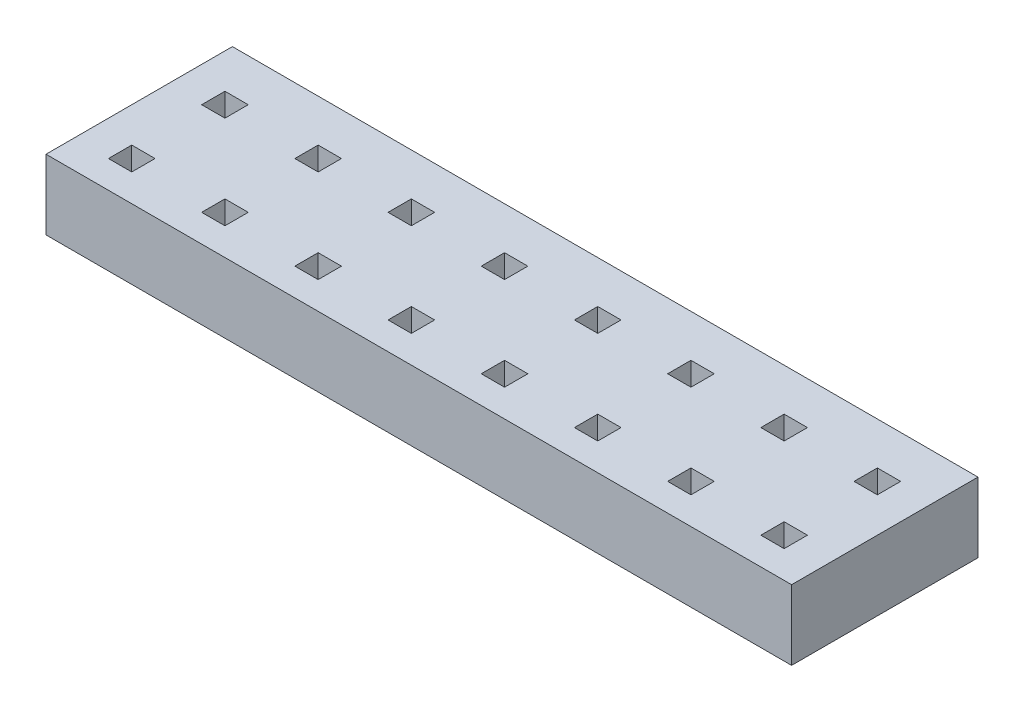
SolidWorks part; units mm, degrees
ref_plane "Front Plane" through (0, 0, 0) normal (0, 0, 1) x (1, 0, 0)
ref_plane "Top Plane" through (0, 0, 0) normal (0, 1, 0) x (1, 0, 0)
ref_plane "Right Plane" through (0, 0, 0) normal (1, 0, 0) x (0, 0, -1)
sketch "Sketch1" plane through (0, 0, 0) normal (0, 1, 0) x (1, 0, 0)
  line L1 (0, 0) -> (16, 0)
  line L2 (0, 0) -> (0, 4)
  line L3 (0, 4) -> (16, 4)
  line L4 (16, 0) -> (16, 4)
extrude "Boss-Extrude1" add sketch "Sketch1" along normal blind 1.5
sketch "Sketch2" plane through (0, 1.5, 0) normal (0, 1, 0) x (1, 0, 0)
  line L0 (2.75, 3.09) -> (3.25, 3.09)
  line L1 (0.75, 3.09) -> (1.25, 3.09)
  line L2 (0.75, 3.09) -> (0.75, 2.59)
  line L3 (0.75, 2.59) -> (1.25, 2.59)
  line L4 (1.25, 3.09) -> (1.25, 2.59)
  line L5 (2.75, 3.09) -> (2.75, 2.59)
  line L6 (2.75, 2.59) -> (3.25, 2.59)
  line L7 (3.25, 3.09) -> (3.25, 2.59)
  line L8 (4.75, 3.09) -> (5.25, 3.09)
  line L9 (4.75, 3.09) -> (4.75, 2.59)
  line L10 (4.75, 2.59) -> (5.25, 2.59)
  line L11 (5.25, 3.09) -> (5.25, 2.59)
  line L12 (6.75, 3.09) -> (7.25, 3.09)
  line L13 (6.75, 3.09) -> (6.75, 2.59)
  line L14 (6.75, 2.59) -> (7.25, 2.59)
  line L15 (7.25, 3.09) -> (7.25, 2.59)
  line L16 (8.75, 3.09) -> (9.25, 3.09)
  line L17 (8.75, 3.09) -> (8.75, 2.59)
  line L18 (8.75, 2.59) -> (9.25, 2.59)
  line L19 (9.25, 3.09) -> (9.25, 2.59)
  line L20 (10.75, 3.09) -> (11.25, 3.09)
  line L21 (10.75, 3.09) -> (10.75, 2.59)
  line L22 (10.75, 2.59) -> (11.25, 2.59)
  line L23 (11.25, 3.09) -> (11.25, 2.59)
  line L24 (12.75, 3.09) -> (13.25, 3.09)
  line L25 (12.75, 3.09) -> (12.75, 2.59)
  line L26 (12.75, 2.59) -> (13.25, 2.59)
  line L27 (13.25, 3.09) -> (13.25, 2.59)
  line L28 (14.75, 3.09) -> (15.25, 3.09)
  line L29 (14.75, 3.09) -> (14.75, 2.59)
  line L30 (14.75, 2.59) -> (15.25, 2.59)
  line L31 (15.25, 3.09) -> (15.25, 2.59)
  line L32 (16.75, 3.09) -> (17.25, 3.09)
  line L33 (16.75, 3.09) -> (16.75, 2.59)
  line L34 (16.75, 2.59) -> (17.25, 2.59)
  line L35 (17.25, 3.09) -> (17.25, 2.59)
  line L36 (18.75, 3.09) -> (19.25, 3.09)
  line L37 (18.75, 3.09) -> (18.75, 2.59)
  line L38 (18.75, 2.59) -> (19.25, 2.59)
  line L39 (19.25, 3.09) -> (19.25, 2.59)
  line L40 (20.75, 3.09) -> (21.25, 3.09)
  line L41 (20.75, 3.09) -> (20.75, 2.59)
  line L42 (20.75, 2.59) -> (21.25, 2.59)
  line L43 (21.25, 3.09) -> (21.25, 2.59)
  line L44 (22.75, 3.09) -> (23.25, 3.09)
  line L45 (22.75, 3.09) -> (22.75, 2.59)
  line L46 (22.75, 2.59) -> (23.25, 2.59)
  line L47 (23.25, 3.09) -> (23.25, 2.59)
  line L48 (24.75, 3.09) -> (25.25, 3.09)
  line L49 (24.75, 3.09) -> (24.75, 2.59)
  line L50 (24.75, 2.59) -> (25.25, 2.59)
  line L51 (25.25, 3.09) -> (25.25, 2.59)
  line L52 (26.75, 3.09) -> (27.25, 3.09)
  line L53 (26.75, 3.09) -> (26.75, 2.59)
  line L54 (26.75, 2.59) -> (27.25, 2.59)
  line L55 (27.25, 3.09) -> (27.25, 2.59)
  line L56 (28.75, 3.09) -> (29.25, 3.09)
  line L57 (28.75, 3.09) -> (28.75, 2.59)
  line L58 (28.75, 2.59) -> (29.25, 2.59)
  line L59 (29.25, 3.09) -> (29.25, 2.59)
  line L60 (30.75, 3.09) -> (31.25, 3.09)
  line L61 (30.75, 3.09) -> (30.75, 2.59)
  line L62 (30.75, 2.59) -> (31.25, 2.59)
  line L63 (31.25, 3.09) -> (31.25, 2.59)
  line L64 (32.75, 3.09) -> (33.25, 3.09)
  line L65 (32.75, 3.09) -> (32.75, 2.59)
  line L66 (32.75, 2.59) -> (33.25, 2.59)
  line L67 (33.25, 3.09) -> (33.25, 2.59)
  line L68 (34.75, 3.09) -> (35.25, 3.09)
  line L69 (34.75, 3.09) -> (34.75, 2.59)
  line L70 (34.75, 2.59) -> (35.25, 2.59)
  line L71 (35.25, 3.09) -> (35.25, 2.59)
  line L72 (0.75, 1.09) -> (1.25, 1.09)
  line L73 (0.75, 1.09) -> (0.75, 0.59)
  line L74 (0.75, 0.59) -> (1.25, 0.59)
  line L75 (1.25, 1.09) -> (1.25, 0.59)
  line L76 (2.75, 1.09) -> (3.25, 1.09)
  line L77 (2.75, 1.09) -> (2.75, 0.59)
  line L78 (2.75, 0.59) -> (3.25, 0.59)
  line L79 (3.25, 1.09) -> (3.25, 0.59)
  line L80 (4.75, 1.09) -> (5.25, 1.09)
  line L81 (4.75, 1.09) -> (4.75, 0.59)
  line L82 (4.75, 0.59) -> (5.25, 0.59)
  line L83 (5.25, 1.09) -> (5.25, 0.59)
  line L84 (6.75, 1.09) -> (7.25, 1.09)
  line L85 (6.75, 1.09) -> (6.75, 0.59)
  line L86 (6.75, 0.59) -> (7.25, 0.59)
  line L87 (7.25, 1.09) -> (7.25, 0.59)
  line L88 (8.75, 1.09) -> (9.25, 1.09)
  line L89 (8.75, 1.09) -> (8.75, 0.59)
  line L90 (8.75, 0.59) -> (9.25, 0.59)
  line L91 (9.25, 1.09) -> (9.25, 0.59)
  line L92 (10.75, 1.09) -> (11.25, 1.09)
  line L93 (10.75, 1.09) -> (10.75, 0.59)
  line L94 (10.75, 0.59) -> (11.25, 0.59)
  line L95 (11.25, 1.09) -> (11.25, 0.59)
  line L96 (12.75, 1.09) -> (13.25, 1.09)
  line L97 (12.75, 1.09) -> (12.75, 0.59)
  line L98 (12.75, 0.59) -> (13.25, 0.59)
  line L99 (13.25, 1.09) -> (13.25, 0.59)
  line L100 (14.75, 1.09) -> (15.25, 1.09)
  line L101 (14.75, 1.09) -> (14.75, 0.59)
  line L102 (14.75, 0.59) -> (15.25, 0.59)
  line L103 (15.25, 1.09) -> (15.25, 0.59)
  line L104 (16.75, 1.09) -> (17.25, 1.09)
  line L105 (16.75, 1.09) -> (16.75, 0.59)
  line L106 (16.75, 0.59) -> (17.25, 0.59)
  line L107 (17.25, 1.09) -> (17.25, 0.59)
  line L108 (18.75, 1.09) -> (19.25, 1.09)
  line L109 (18.75, 1.09) -> (18.75, 0.59)
  line L110 (18.75, 0.59) -> (19.25, 0.59)
  line L111 (19.25, 1.09) -> (19.25, 0.59)
  line L112 (20.75, 1.09) -> (21.25, 1.09)
  line L113 (20.75, 1.09) -> (20.75, 0.59)
  line L114 (20.75, 0.59) -> (21.25, 0.59)
  line L115 (21.25, 1.09) -> (21.25, 0.59)
  line L116 (22.75, 1.09) -> (23.25, 1.09)
  line L117 (22.75, 1.09) -> (22.75, 0.59)
  line L118 (22.75, 0.59) -> (23.25, 0.59)
  line L119 (23.25, 1.09) -> (23.25, 0.59)
  line L120 (24.75, 1.09) -> (25.25, 1.09)
  line L121 (24.75, 1.09) -> (24.75, 0.59)
  line L122 (24.75, 0.59) -> (25.25, 0.59)
  line L123 (25.25, 1.09) -> (25.25, 0.59)
  line L124 (26.75, 1.09) -> (27.25, 1.09)
  line L125 (26.75, 1.09) -> (26.75, 0.59)
  line L126 (26.75, 0.59) -> (27.25, 0.59)
  line L127 (27.25, 1.09) -> (27.25, 0.59)
  line L128 (28.75, 1.09) -> (29.25, 1.09)
  line L129 (28.75, 1.09) -> (28.75, 0.59)
  line L130 (28.75, 0.59) -> (29.25, 0.59)
  line L131 (29.25, 1.09) -> (29.25, 0.59)
  line L132 (30.75, 1.09) -> (31.25, 1.09)
  line L133 (30.75, 1.09) -> (30.75, 0.59)
  line L134 (30.75, 0.59) -> (31.25, 0.59)
  line L135 (31.25, 1.09) -> (31.25, 0.59)
  line L136 (32.75, 1.09) -> (33.25, 1.09)
  line L137 (32.75, 1.09) -> (32.75, 0.59)
  line L138 (32.75, 0.59) -> (33.25, 0.59)
  line L139 (33.25, 1.09) -> (33.25, 0.59)
  line L140 (34.75, 1.09) -> (35.25, 1.09)
  line L141 (34.75, 1.09) -> (34.75, 0.59)
  line L142 (34.75, 0.59) -> (35.25, 0.59)
  line L143 (35.25, 1.09) -> (35.25, 0.59)
  dimension "D1" = 18
  dimension "D2" = 2
extrude "Cut-Extrude1" cut sketch "Sketch2" against normal blind 2
